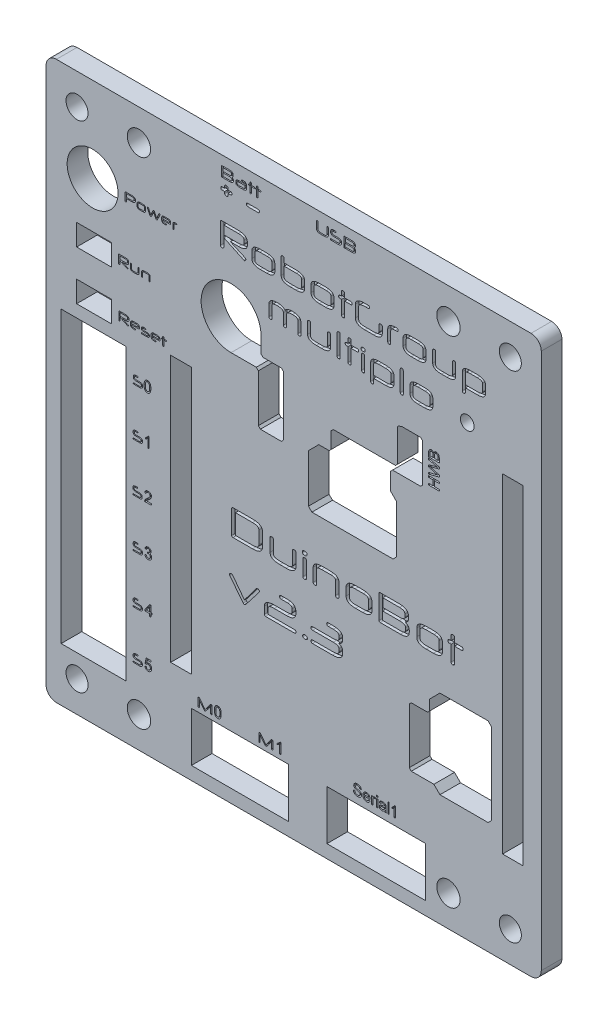
SolidWorks part; units mm, degrees
ref_plane "Alzado" through (0, 0, 0) normal (0, 0, 1) x (1, 0, 0)
ref_plane "Planta" through (0, 0, 0) normal (0, 1, 0) x (1, 0, 0)
ref_plane "Vista lateral" through (0, 0, 0) normal (1, 0, 0) x (0, 0, -1)
sketch "Model" plane through (0, 0, 0) normal (0, 0, 1) x (1, 0, 0)
  line L0 (79.0698, 220.6038) -> (79.0698, 298.6084)
  line L1 (7.0674, 298.6084) -> (7.0674, 220.6038)
  line L2 (8.5674, 219.1038) -> (77.5698, 219.1038)
  line L3 (77.5698, 300.1084) -> (8.5674, 300.1084)
  line L4 (76.4432, 280.3563) -> (73.4432, 280.3563)
  line L5 (76.4432, 232.4763) -> (76.4432, 280.3563)
  line L6 (73.4432, 232.4763) -> (76.4432, 232.4763)
  line L7 (73.4432, 280.3563) -> (73.4432, 232.4763)
  line L8 (28.1808, 232.4801) -> (28.1808, 271.1578)
  line L9 (25.1808, 232.4801) -> (28.1808, 232.4801)
  line L10 (25.1808, 271.1578) -> (25.1808, 232.4801)
  line L11 (9.2551, 269.0104) -> (9.2563, 226.8832)
  line L12 (18.685, 269.0104) -> (18.6863, 226.8832)
  line L13 (18.685, 269.0104) -> (9.2551, 269.0104)
  line L14 (18.6863, 226.8832) -> (9.2563, 226.8832)
  line L15 (37.929, 268.6584) -> (37.9301, 275.5694)
  line L16 (41.2725, 268.3584) -> (38.2289, 268.3584)
  line L17 (41.5725, 277.3009) -> (41.5725, 268.6584)
  line L18 (38.6121, 277.6009) -> (41.2725, 277.6009)
  line L19 (47.8995, 221.0056) -> (62.2048, 221.0056)
  line L20 (62.2048, 228.2055) -> (47.8995, 228.2055)
  line L21 (47.8995, 228.2055) -> (47.8995, 221.0056)
  line L22 (62.2048, 221.0056) -> (62.2048, 228.2055)
  line L23 (28.1941, 221.0056) -> (42.2994, 221.0056)
  line L24 (42.2994, 228.2055) -> (28.1941, 228.2055)
  line L25 (28.1941, 228.2055) -> (28.1941, 221.0056)
  line L26 (42.2994, 221.0056) -> (42.2994, 228.2055)
  line L27 (16.6077, 273.8998) -> (11.5077, 273.8998)
  line L28 (16.6077, 270.7998) -> (16.6077, 273.8998)
  line L29 (11.5077, 270.7998) -> (16.6077, 270.7998)
  line L30 (11.5077, 273.8998) -> (11.5077, 270.7998)
  line L31 (16.6077, 281.0451) -> (11.5077, 281.0451)
  line L32 (16.6077, 277.9451) -> (16.6077, 281.0451)
  line L33 (11.5077, 277.9451) -> (16.6077, 277.9451)
  line L34 (11.5077, 281.0451) -> (11.5077, 277.9451)
  line L35 (25.1808, 271.1578) -> (28.1808, 271.1578)
  line L36 (45.2171, 262.1628) -> (45.7171, 261.6628)
  line L37 (57.5171, 261.6628) -> (58.0171, 262.1628)
  line L38 (45.2171, 269.1628) -> (46.7171, 270.6628)
  line L39 (48.226, 270.6628) -> (46.7171, 270.6628)
  line L40 (45.2171, 269.1628) -> (45.2171, 262.1628)
  line L41 (58.0171, 262.1628) -> (58.0171, 269.1628)
  line L42 (45.7171, 261.6628) -> (57.5171, 261.6628)
  line L43 (57.8731, 273.6225) -> (48.826, 273.6225)
  line L44 (57.1392, 270.0406) -> (57.1392, 272.0907)
  line L45 (48.526, 270.9628) -> (48.526, 273.3225)
  line L46 (48.526, 270.9628) -> (48.226, 270.6628)
  line L47 (48.826, 273.6225) -> (48.526, 273.3225)
  line L48 (58.0171, 269.1628) -> (57.1392, 270.0406)
  line L49 (57.1392, 270.9628) -> (57.1392, 272.5218)
  line L50 (58.1732, 273.9225) -> (58.1739, 278.6843)
  line L51 (61.5165, 272.8218) -> (57.4392, 272.8218)
  line L52 (61.8165, 278.6843) -> (61.8165, 273.1218)
  line L53 (58.774, 278.9843) -> (61.5165, 278.9843)
  line L54 (71.3319, 235.3872) -> (64.3319, 235.3872)
  line L55 (71.3319, 248.1872) -> (71.8319, 247.6872)
  line L56 (71.8319, 235.8872) -> (71.3319, 235.3872)
  line L57 (64.3319, 248.1872) -> (62.8319, 246.6872)
  line L58 (62.8319, 245.1782) -> (62.8319, 246.6872)
  line L59 (64.3319, 248.1872) -> (71.3319, 248.1872)
  line L60 (71.8319, 247.6872) -> (71.8319, 235.8872)
  line L61 (59.8723, 236.5651) -> (59.8723, 244.5782)
  line L62 (63.4541, 236.2651) -> (61.4041, 236.2651)
  line L63 (62.5319, 244.8782) -> (60.1723, 244.8782)
  line L64 (62.5319, 244.8782) -> (62.8319, 245.1782)
  line L65 (59.8723, 244.5782) -> (60.1723, 244.8782)
  line L66 (64.3319, 235.3872) -> (63.4541, 236.2651)
  line L67 (62.5319, 236.2651) -> (60.1723, 236.2651)
  line L68 (59.8723, 236.5651) -> (60.1723, 236.2651)
  line L69 (41.5725, 277.3009) -> (41.2725, 277.6009)
  line L70 (41.5725, 268.6584) -> (41.2725, 268.3584)
  line L71 (38.2289, 268.3584) -> (37.929, 268.6584)
  line L72 (58.1739, 278.6843) -> (58.2618, 278.7722)
  line L73 (58.2618, 278.7722) -> (58.774, 278.9843)
  line L74 (61.5165, 278.9843) -> (61.8165, 278.6843)
  line L75 (61.5165, 272.8218) -> (61.8165, 273.1218)
  line L76 (33.9621, 275.8694) -> (37.6301, 275.8694)
  line L77 (38.3121, 280.2194) -> (38.3121, 277.9009)
  line L78 (38.3121, 277.9009) -> (38.6121, 277.6009)
  line L79 (37.6301, 275.8694) -> (37.9301, 275.5694)
  line L80 (57.8731, 273.6225) -> (58.1732, 273.9225)
  line L81 (57.4392, 272.8218) -> (57.1392, 272.5218)
  arc A0 (8.5674, 300.1084) -> (7.0674, 298.6084) centre (8.5674, 298.6084) ccw
  arc A1 (7.0674, 220.6038) -> (8.5674, 219.1038) centre (8.5674, 220.6038) ccw
  arc A2 (77.5698, 219.1038) -> (79.0698, 220.6038) centre (77.5698, 220.6038) ccw
  arc A3 (79.0698, 298.6084) -> (77.5698, 300.1084) centre (77.5698, 298.6084) ccw
  circle A4 centre (68.3041, 284.2311) radius 1
  circle A5 centre (13.8303, 287.7239) radius 3.7
  circle A6 centre (20.5667, 223.6035) radius 1.7
  circle A7 centre (65.5701, 223.6035) radius 1.7
  circle A8 centre (11.5671, 223.6035) radius 1.6003
  circle A9 centre (74.5698, 223.6035) radius 1.6003
  circle A10 centre (20.5667, 295.6084) radius 1.7
  circle A11 centre (65.5701, 295.6084) radius 1.7
  circle A12 centre (74.5698, 295.6084) radius 1.6003
  circle A13 centre (11.5671, 295.6084) radius 1.6003
  arc A14 (38.3121, 280.2194) -> (33.9621, 275.8694) centre (33.9621, 280.2194) ccw
extrude "Saliente-Extruir1" add sketch "Model" along normal blind 3 contours L0 A3 L3 A0 L1 A1 L2 A2 A14 L77 L78 L18 L69 L17 L70 L16 L71 L15 L79 L76 A13 A12 A11 A10 A9 A8 A7 A6 A5 A4 L51 L81 L49 L44 L48 L41 L37 L42 region at (44.5131, 262.02, 0)
sketch "Croquis1" plane through (0, 0, 3) normal (0, 0, 1) x (1, 0, 0)
  line L0 (16.6077, 272.3498) -> (17.6077, 272.3498) construction
  line L1 (16.6077, 270.7998) -> (16.6077, 273.8998) construction
  line L2 (16.6077, 279.4951) -> (17.6077, 279.4951) construction
  line L3 (16.6077, 277.9451) -> (16.6077, 281.0451) construction
  line L4 (17.6077, 279.4951) -> (17.6077, 272.3498) construction
  line L5 (13.8303, 287.7239) -> (17.5303, 287.7239) construction
  line L6 (17.5303, 287.7239) -> (18.5303, 287.7239) construction
  line L7 (18.685, 269.0104) -> (19.685, 269.0104) construction
  line L8 (18.685, 269.0104) -> (18.6863, 226.8832) construction
  line L9 (18.6863, 226.8832) -> (19.685, 226.8832) construction
  line L10 (19.685, 226.8832) -> (19.685, 230.4032) construction
  line L11 (19.685, 230.4032) -> (19.685, 233.9132) construction
  line L12 (19.685, 233.9132) -> (19.685, 237.4232) construction
  line L13 (19.685, 237.4232) -> (19.685, 240.9332) construction
  line L14 (19.685, 240.9332) -> (19.685, 244.4432) construction
  line L15 (19.685, 244.4432) -> (19.685, 247.9532) construction
  line L16 (19.685, 247.9532) -> (19.685, 251.4632) construction
  line L17 (19.685, 251.4632) -> (19.685, 254.9732) construction
  line L18 (19.685, 254.9732) -> (19.685, 258.4832) construction
  line L19 (19.685, 258.4832) -> (19.685, 261.9932) construction
  line L20 (19.685, 261.9932) -> (19.685, 265.5032) construction
  line L21 (19.685, 265.5032) -> (19.685, 269.0104) construction
  line L22 (29.0148, 228.8708) -> (42.1608, 228.8708) construction
  line L23 (46.2174, 297.3009) -> (7.0674, 297.3009) construction
  line L24 (7.0674, 298.6084) -> (7.0674, 220.6038) construction
  circle A0 centre (13.8303, 287.7239) radius 3.7 construction
  text T0 "Reset" font "Neuropol X Free" height in points 6
  text T1 "Run" font "Neuropol X Free" height in points 6
  text T2 "Power" font "Neuropol X Free" height in points 6
  text T3 "S" font "Neuropol X Free" height in points 6
  text T4 "S" font "Neuropol X Free" height in points 6
  text T5 "S" font "Neuropol X Free" height in points 6
  text T6 "S" font "Neuropol X Free" height in points 6
  text T7 "S" font "Neuropol X Free" height in points 6
  text T8 "S" font "Neuropol X Free" height in points 6
  text T9 "0" font "Arial" height in points 6
  text T10 "1" font "Arial" height in points 6
  text T11 "2" font "Arial" height in points 6
  text T12 "3" font "Arial" height in points 6
  text T13 "4" font "Arial" height in points 6
  text T14 "5" font "Arial" height in points 6
  text T15 "Serial1" font "Arial" height in points 6
  text T16 "M" font "Neuropol X Free" height in points 6
  text T17 "M" font "Neuropol X Free" height in points 6
  text T18 "0" font "Arial" height in points 6
  text T19 "1" font "Arial" height in points 6
  text T20 "USB" font "Neuropol X Free" height in points 7
  text T21 "Batt" font "Neuropol X Free" height in points 7
  text T22 "+ -" font "Neuropol X Free" height in points 14
  dimension "D1" = 1
  dimension "D2" = 1
  dimension "D4" = 3.52
  dimension "D3" = 1
  dimension "D5" = 3.51
  dimension "D6" = 3.51
  dimension "D7" = 3.51
  dimension "D8" = 3.51
  dimension "D9" = 3.51
  dimension "D10" = 3.51
  dimension "D11" = 3.51
  dimension "D12" = 3.51
  dimension "D13" = 3.51
  dimension "D14" = 3.51
  dimension "D16" = 3.5072
extrude "Cortar-Extruir1" cut sketch "Croquis1" against normal blind 0.5
sketch "Croquis2" plane through (0, 0, 3) normal (0, 0, 1) x (1, 0, 0)
  text T0 "RobotGroup" font "Neuropol X Free" height in points 16
  text T1 "multiplo" font "Neuropol X Free" height in points 16
  text T2 "DuinoBot\r\nv2.3" font "Neuropol X Free" height in points 18
extrude "Cortar-Extruir2" cut sketch "Croquis2" against normal blind 0.5
sketch "Croquis4" plane through (0, 0, 3) normal (0, 0, 1) x (1, 0, 0)
  line L0 (61.8165, 273.1218) -> (64.2404, 273.1218) construction
  line L1 (64.2404, 273.1218) -> (64.2404, 278.6839) construction
  text T0 "HWB" font "Arial" height in points 6
extrude "Cortar-Extruir3" cut sketch "Croquis4" against normal blind 0.5
